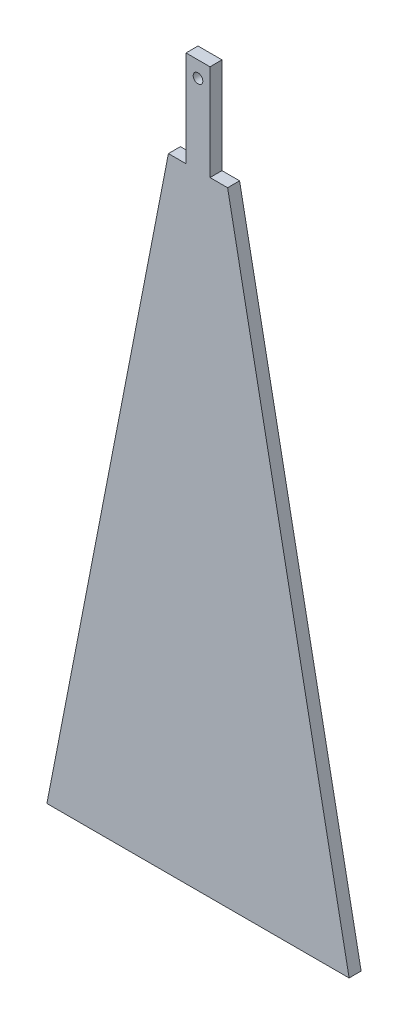
SolidWorks part; units mm, degrees
ref_plane "Front Plane" through (0, 0, 0) normal (0, 0, 1) x (1, 0, 0)
ref_plane "Top Plane" through (0, 0, 0) normal (0, 1, 0) x (1, 0, 0)
ref_plane "Right Plane" through (0, 0, 0) normal (1, 0, 0) x (0, 0, -1)
sketch "Sketch1" plane through (0, 0, 0) normal (0, 0, 1) x (1, 0, 0)
  line L0 (-31.5, 0) -> (31.5, 0)
  line L1 (31.5, 0) -> (6.1691, 130)
  line L2 (6.1691, 130) -> (2.5, 130)
  line L3 (2.5, 130) -> (2.5, 150)
  line L4 (2.5, 150) -> (-2.5, 150)
  line L5 (-2.5, 150) -> (-2.5, 130)
  line L6 (-2.5, 130) -> (-6.1691, 130)
  line L7 (-6.1691, 130) -> (-31.5, 0)
  point P4 (0, 0)
  point P8 (0, 150)
  point P11 (0, 0)
  point P12 (0, 0)
  point P13 (-8.8545, 130)
  point P14 (6.0643, 130)
  point P15 (-6.1691, 130)
  dimension "D1" = 63
  dimension "D2" = 150
  dimension "D3" = 20
  dimension "D4" = 20
  dimension "D5" = 5
base flange "Base-Flange1" sketch "Sketch1" thickness 2.5 reverse thickness direction no parameters "D1"=1
sketch "Sketch8" plane through (0, 0, 0) normal (0, 0, 1) x (1, 0, 0)
  circle A0 centre (0, 146.6618) radius 1
  point P2 (0, 146.6618)
  dimension "D1" = 2
extrude "Cut-Extrude1" cut sketch "Sketch8" against normal blind 10
sketch "Bend-Lines1" [suppressed] plane through (0, 0, 0) normal (0, 1, 0) x (1, 0, 0)
sketch "Bounding-Box1" [suppressed] plane through (0, 0, 0) normal (0, 1, 0) x (1, 0, 0)
sheet metal parameters "Sheet-Metal1" thickness 2.5 parameters "D1"=1
flat pattern "Flat-Pattern1" [suppressed]
sketch "Bend-Lines2" plane through (0, 0, 0) normal (0, 1, 0) x (1, 0, 0)
sketch3d "Bounding-Box2" [suppressed]
  line L0 (31.5, 150, 0) -> (31.5, 0, 0) construction
  line L1 (-31.5, 150, 0) -> (-31.5, 0, 0) construction
  line L2 (31.5, 150, 0) -> (-31.5, 150, 0) construction
  line L3 (31.5, 0, 0) -> (-31.5, 0, 0) construction
sheet metal parameters "Sheet-Metal3" thickness 2.5 parameters "D1"=1
flat pattern "Flat-Pattern1"
sketch "Bend-Lines2" plane through (0, 0, 0) normal (0, 1, 0) x (1, 0, 0)
sketch3d "Bounding-Box2" [suppressed]
  line L0 (31.5, 150, 0) -> (31.5, 0, 0) construction
  line L1 (-31.5, 150, 0) -> (-31.5, 0, 0) construction
  line L2 (31.5, 150, 0) -> (-31.5, 150, 0) construction
  line L3 (31.5, 0, 0) -> (-31.5, 0, 0) construction
